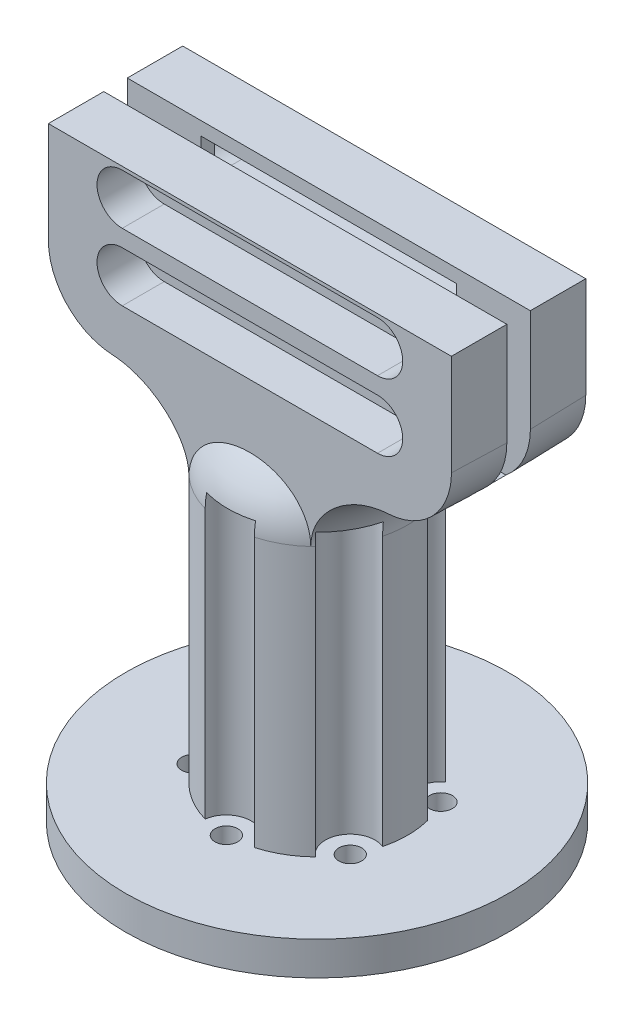
SolidWorks part; units mm, degrees
ref_plane "前视基准面" through (0, 0, 0) normal (0, 0, 1) x (1, 0, 0)
ref_plane "上视基准面" through (0, 0, 0) normal (0, 1, 0) x (1, 0, 0)
ref_plane "右视基准面" through (0, 0, 0) normal (1, 0, 0) x (0, 0, -1)
sketch "草图1" plane through (0, 0, 0) normal (0, 1, 0) x (1, 0, 0)
  circle A0 centre (0, 0) radius 13.5 construction
  circle A1 centre (0, 0) radius 28.5
  circle A2 centre (0, 13.5) radius 1.7
  circle A3 centre (11.6913, 6.75) radius 1.7
  circle A4 centre (11.6913, -6.75) radius 1.7
  circle A5 centre (0, -13.5) radius 1.7
  circle A6 centre (-11.6913, -6.75) radius 1.7
  circle A7 centre (-11.6913, 6.75) radius 1.7
  point P18 (0, 0)
  dimension "D1" = 27
  dimension "D2" = 57
  dimension "D3" = 3.4
  dimension "D4" = 6
extrude "凸台-拉伸1" add sketch "草图1" along normal blind 5
sketch "草图2" plane through (0, 5, 0) normal (0, 1, 0) x (1, 0, 0)
  circle A0 centre (0, 0) radius 13.5
  dimension "D1" = 27
extrude "凸台-拉伸2" add sketch "草图2" along normal blind 50
sketch "草图3" plane through (0, 55, 0) normal (0, 1, 0) x (1, 0, 0)
  line L1 (-30, 10) -> (30, 10)
  line L2 (-30, 10) -> (-30, -10)
  line L3 (-30, -10) -> (30, -10)
  line L4 (30, 10) -> (30, -10)
  line L5 (-30, 10) -> (30, -10) construction
  line L6 (-30, -10) -> (30, 10) construction
  point P0 (0, 0)
  dimension "D1" = 60
  dimension "D2" = 20
extrude "凸台-拉伸3" add sketch "草图3" along normal blind 25
sketch "草图4" plane through (0, 80, 0) normal (0, 1, 0) x (1, 0, 0)
  line L1 (-33.8699, 1.75) -> (33.8699, 1.75)
  line L2 (-33.8699, 1.75) -> (-33.8699, -1.75)
  line L3 (-33.8699, -1.75) -> (33.8699, -1.75)
  line L4 (33.8699, 1.75) -> (33.8699, -1.75)
  line L5 (-33.8699, 1.75) -> (33.8699, -1.75) construction
  line L6 (-33.8699, -1.75) -> (33.8699, 1.75) construction
  point P0 (0, 0)
  dimension "D1" = 3.5
extrude "切除-拉伸1" cut sketch "草图4" against normal blind 23
sketch "草图5" plane through (0, 0, -10) normal (0, 0, -1) x (-1, 0, 0)
  line L0 (0, -4.6007) -> (0, 100.7282) construction
  line L1 (-30, 80) -> (30, 80) construction
  line L2 (-19, 73.5) -> (19, 73.5)
  line L3 (-19, 73.5) -> (-19, 78)
  line L4 (-19, 78) -> (19, 78)
  line L5 (19, 73.5) -> (19, 78)
  line L6 (-19, 73.5) -> (19, 78) construction
  line L7 (-19, 78) -> (19, 73.5) construction
  line L9 (-19, 63.5) -> (19, 63.5)
  line L10 (-19, 63.5) -> (-19, 68)
  line L11 (-19, 68) -> (19, 68)
  line L12 (19, 63.5) -> (19, 68)
  line L13 (-19, 63.5) -> (19, 68) construction
  line L14 (-19, 68) -> (19, 63.5) construction
  point P3 (0, 75.75)
  point P10 (0, 65.75)
  dimension "D1" = 2
  dimension "D2" = 4.5
  dimension "D3" = 38
  dimension "D4" = 10
  dimension "D5" = 38
  dimension "D6" = 4.5
extrude "切除-拉伸2" cut sketch "草图5" against normal blind 43
sketch "草图6" plane through (0, 0, -10) normal (0, 0, -1) x (-1, 0, 0)
  line L0 (-19, 68) -> (-19, 63.5) construction
  line L1 (19, 63.5) -> (19, 68) construction
  line L2 (-19, 78) -> (-19, 73.5) construction
  line L3 (19, 73.5) -> (19, 78) construction
  line L5 (-19, 62) -> (19, 62)
  line L7 (-19, 69.5) -> (19, 69.5)
  line L9 (-19, 72) -> (19, 72)
  line L11 (-19, 79.5) -> (19, 79.5)
  arc A0 (-19, 69.5) -> (-19, 62) centre (-19, 65.75) ccw
  arc A1 (19, 62) -> (19, 69.5) centre (19, 65.75) ccw
  arc A2 (-19, 79.5) -> (-19, 72) centre (-19, 75.75) ccw
  arc A3 (19, 72) -> (19, 79.5) centre (19, 75.75) ccw
  dimension "D1" = 7.5
  dimension "D2" = 7.5
  dimension "D3" = 7.5
  dimension "D4" = 7.5
extrude "切除-拉伸3" cut sketch "草图6" against normal offset from surface (6.25 mm away) 2 up to face at (0, 65.75, -1.75)
sketch "草图7" plane through (0, 0, 10) normal (0, 0, 1) x (1, 0, 0)
  line L0 (19, 78) -> (19, 73.5) construction
  line L1 (19, 68) -> (19, 63.5) construction
  line L2 (-19, 73.5) -> (-19, 78) construction
  line L3 (-19, 63.5) -> (-19, 68) construction
  line L5 (19, 79.5) -> (-19, 79.5)
  line L7 (19, 72) -> (-19, 72)
  line L9 (19, 69.5) -> (-19, 69.5)
  line L11 (19, 62) -> (-19, 62)
  arc A0 (19, 72) -> (19, 79.5) centre (19, 75.75) ccw
  arc A1 (19, 62) -> (19, 69.5) centre (19, 65.75) ccw
  arc A2 (-19, 79.5) -> (-19, 72) centre (-19, 75.75) ccw
  arc A3 (-19, 69.5) -> (-19, 62) centre (-19, 65.75) ccw
  dimension "D1" = 7.5
  dimension "D2" = 7.5
  dimension "D3" = 7.5
  dimension "D4" = 7.5
extrude "切除-拉伸4" cut sketch "草图7" against normal offset from surface (6.25 mm away) 2 up to face at (0, 65.75, 1.75)
fillet "圆角1" radius 10 2 edges at (0, 55, -13.5) (0, 55, 13.5)
fillet "圆角2" radius 10 2 edges at (13.5, 55, 0) (-13.5, 55, 0)
fillet "圆角3" radius 10 2 edges at (-30, 55, 0) (30, 55, 0)
sketch "草图8" plane through (0, 5, 0) normal (0, 1, 0) x (1, 0, 0)
  circle A0 centre (0, -13.5) radius 3.7
  arc A1 (-9.0692, -10) -> (9.0692, -10) centre (0, 0) ccw construction
  circle A2 centre (0, 13.5) radius 3.7
  arc A3 (9.0692, 10) -> (-9.0692, 10) centre (0, 0) ccw construction
  circle A4 centre (11.6913, 6.75) radius 3.7
  circle A5 centre (11.6913, -6.75) radius 3.7
  circle A6 centre (-11.6913, 6.75) radius 3.7
  arc A7 (-10.7503, 8.1658) -> (-12.447, 5.2272) centre (0, 0) ccw construction
  circle A8 centre (-11.6913, -6.75) radius 3.7
  arc A9 (-12.447, -5.2272) -> (-10.7503, -8.1658) centre (0, 0) ccw construction
  dimension "D1" = 7.4
  dimension "D2" = 7.4
  dimension "D3" = 7.4
  dimension "D4" = 7.4
  dimension "D5" = 7.4
  dimension "D6" = 7.4
extrude "切除-拉伸5" cut sketch "草图8" along normal blind 42
